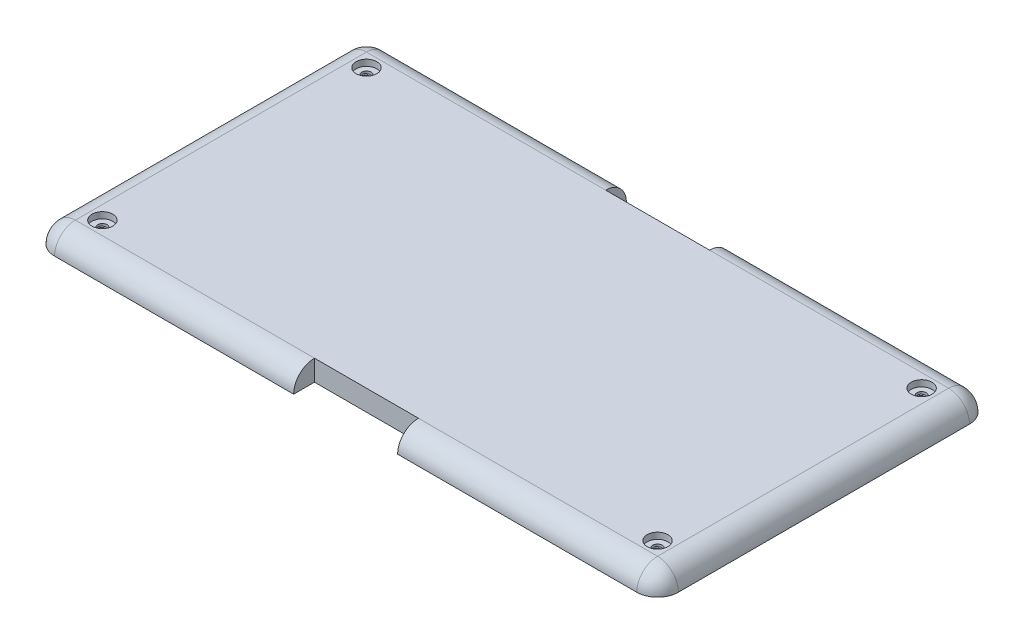
SolidWorks part; units mm, degrees
ref_plane "Plan de face" through (0, 0, 0) normal (0, 0, 1) x (1, 0, 0)
ref_plane "Plan de dessus" through (0, 0, 0) normal (0, 1, 0) x (1, 0, 0)
ref_plane "Plan de droite" through (0, 0, 0) normal (1, 0, 0) x (0, 0, -1)
sketch "Esquisse1" plane through (0, 0, 0) normal (0, 1, 0) x (1, 0, 0)
  line L1 (150, 80) -> (-150, 80)
  line L2 (150, 80) -> (150, -80)
  line L3 (150, -80) -> (-150, -80)
  line L4 (-150, 80) -> (-150, -80)
  line L5 (150, 80) -> (-150, -80) construction
  line L6 (150, -80) -> (-150, 80) construction
  point P0 (0, 0)
  dimension "D1" = 300
  dimension "D2" = 160
extrude "Boss.-Extru.1" add sketch "Esquisse1" along normal blind 10
fillet "Congé1" radius 10 1 edges at (-150, 5, -80)
fillet "Congé2" radius 10 3 edges at (-150, 5, 80) (150, 5, 80) (150, 5, -80)
fillet "Congé4" radius 10 8 edges at (-147.0711, 10, -77.0711) (0, 10, -80) (147.0711, 10, -77.0711) (150, 10, 0) (147.0711, 10, 77.0711) (0, 10, 80) (-147.0711, 10, 77.0711) (-150, 10, 0)
sketch "Esquisse2" plane through (0, 10, 0) normal (0, 1, 0) x (1, 0, 0)
  line L0 (-140, -80) -> (140, -80) construction
  line L1 (140, 80) -> (-140, 80) construction
  line L2 (150, -70) -> (150, 70) construction
  line L3 (-150, 70) -> (-150, -70) construction
  circle A0 centre (-133.5, 63.5) radius 5
  circle A1 centre (-133.5, -63.5) radius 5
  circle A2 centre (133.5, -63.5) radius 5
  circle A3 centre (133.5, 63.5) radius 5
  circle A4 centre (133.5, -63.5) radius 2
  dimension "D1" = 10
  dimension "D2" = 10
  dimension "D3" = 10
  dimension "D4" = 10
  dimension "D6" = 16.5
  dimension "D7" = 16.5
  dimension "D8" = 16.5
  dimension "D9" = 16.5
  dimension "D10" = 16.5
  dimension "D13" = 4
  dimension "D5" = 16.5
  dimension "D11" = 16.5
  dimension "D12" = 16.5
extrude "Enlèv. mat.-Extru.1" cut sketch "Esquisse2" against normal blind 3
sketch "Esquisse4" plane through (0, 10, 0) normal (0, 1, 0) x (1, 0, 0)
  circle A0 centre (133.5, -63.5) radius 2.25
  dimension "D1" = 4.5
extrude "Enlèv. mat.-Extru.2" cut sketch "Esquisse4" against normal blind 13
sketch "Esquisse5" plane through (0, 7, 0) normal (0, 1, 0) x (1, 0, 0)
  circle A0 centre (133.5, 63.5) radius 2.25
  circle A1 centre (-133.5, 63.5) radius 2.25
  circle A2 centre (-133.5, -63.5) radius 2.25
  dimension "D1" = 4.5
  dimension "D2" = 4.5
  dimension "D3" = 4.5
extrude "Enlèv. mat.-Extru.3" cut sketch "Esquisse5" against normal blind 13
sketch "Esquisse7" plane through (0, 10, 0) normal (0, 1, 0) x (1, 0, 0)
  line L0 (140, -70) -> (-140, -70) construction
  line L1 (-140, -70) -> (140, -70) construction
  line L2 (-140, -70) -> (140, -70) construction
  line L3 (140, -70) -> (-140, -70) construction
  line L4 (-140, 70) -> (140, 70) construction
  line L5 (0, -70) -> (-25, -70)
  line L6 (0, -70) -> (0, -92.4366)
  line L7 (0, -92.4366) -> (-25, -92.4366)
  line L8 (-25, -70) -> (-25, -92.4366)
  line L9 (0, -70) -> (25, -70)
  line L10 (0, -70) -> (0, -92.4366)
  line L11 (0, -92.4366) -> (25, -92.4366)
  line L12 (25, -70) -> (25, -92.4366)
  line L14 (0, 70) -> (-25, 70)
  line L15 (0, 70) -> (0, 92.8833)
  line L16 (0, 92.8833) -> (-25, 92.8833)
  line L17 (-25, 70) -> (-25, 92.8833)
  line L18 (0, 70) -> (25, 70)
  line L19 (0, 70) -> (0, 92.8833)
  line L20 (0, 92.8833) -> (25, 92.8833)
  line L21 (25, 70) -> (25, 92.8833)
  line M9 (140, 70) -> (-140, 70)
  line M11 (-140, -70) -> (140, -70)
  dimension "D1" = 25
  dimension "D2" = 25
  dimension "D3" = 25
  dimension "D4" = 25
extrude "Enlèv. mat.-Extru.5" cut sketch "Esquisse7" against normal mid plane 50 contours L17 L15 L16 M9 | L21 L20 L15 M9 | L8 L7 L6 M11 | L12 L6 L11 M11
thread "Filetage1" pitch 0.8 start angle 0, offset 1, length 0, pitch 0.8, diameter 4.5
ref_plane "Plan1" through (-135.75, 6, -63.5) normal (0, 0, 1) x (-1, 0, 0)
sketch "Profil de filetage1" plane through (-135.75, 6, -63.5) normal (0, 0, 1) x (-1, 0, 0)
  line L0 (0, 0) -> (0, 0.8) construction
  line L11 (0, 0) -> (0, 0.7)
  line L12 (0, 0.7) -> (-0.433, 0.45)
  line L13 (-0.433, 0.45) -> (-0.433, 0.25)
  line L15 (-0.433, 0.25) -> (0, 0)
  line L17 (-0.433, 0.35) -> (0, 0.35) construction
  point P2 (0, 0)
  dimension "Pitch" = 0.8
  dimension "Profile_Angle" = 60
  dimension "Profile_Land" = 0.2
  dimension "Profile_Height" = 0.433
thread "Filetage2" pitch 0.8 profile "Profil de filetage2" start angle 0, offset 1, length 0, pitch 0.8, diameter 4.5
ref_plane "Plan2" through (-135.75, 6, 63.5) normal (0, 0, 1) x (-1, 0, 0)
sketch "Profil de filetage2" plane through (-135.75, 6, 63.5) normal (0, 0, 1) x (-1, 0, 0)
  line L0 (0, 0) -> (0, 0.8) construction
  line L11 (0, 0) -> (0, 0.7)
  line L12 (0, 0.7) -> (-0.433, 0.45)
  line L13 (-0.433, 0.45) -> (-0.433, 0.25)
  line L15 (-0.433, 0.25) -> (0, 0)
  line L17 (-0.433, 0.35) -> (0, 0.35) construction
  point P2 (0, 0)
  dimension "Pitch" = 0.8
  dimension "Profile_Angle" = 60
  dimension "Profile_Land" = 0.2
  dimension "Profile_Height" = 0.433
thread "Filetage3" pitch 0.8 profile "Profil de filetage3" start angle 0, offset 1, length 0, pitch 0.8, diameter 4.5
ref_plane "Plan3" through (131.25, 6, -63.5) normal (0, 0, 1) x (-1, 0, 0)
sketch "Profil de filetage3" plane through (131.25, 6, -63.5) normal (0, 0, 1) x (-1, 0, 0)
  line L0 (0, 0) -> (0, 0.8) construction
  line L11 (0, 0) -> (0, 0.7)
  line L12 (0, 0.7) -> (-0.433, 0.45)
  line L13 (-0.433, 0.45) -> (-0.433, 0.25)
  line L15 (-0.433, 0.25) -> (0, 0)
  line L17 (-0.433, 0.35) -> (0, 0.35) construction
  point P2 (0, 0)
  dimension "Pitch" = 0.8
  dimension "Profile_Angle" = 60
  dimension "Profile_Land" = 0.2
  dimension "Profile_Height" = 0.433
thread "Filetage4" pitch 0.8 profile "Profil de filetage4" start angle 0, offset 1, length 0, pitch 0.8, diameter 4.5
ref_plane "Plan4" through (131.25, 6, 63.5) normal (0, 0, 1) x (-1, 0, 0)
sketch "Profil de filetage4" plane through (131.25, 6, 63.5) normal (0, 0, 1) x (-1, 0, 0)
  line L0 (0, 0) -> (0, 0.8) construction
  line L11 (0, 0) -> (0, 0.7)
  line L12 (0, 0.7) -> (-0.433, 0.45)
  line L13 (-0.433, 0.45) -> (-0.433, 0.25)
  line L15 (-0.433, 0.25) -> (0, 0)
  line L17 (-0.433, 0.35) -> (0, 0.35) construction
  point P2 (0, 0)
  dimension "Pitch" = 0.8
  dimension "Profile_Angle" = 60
  dimension "Profile_Land" = 0.2
  dimension "Profile_Height" = 0.433
